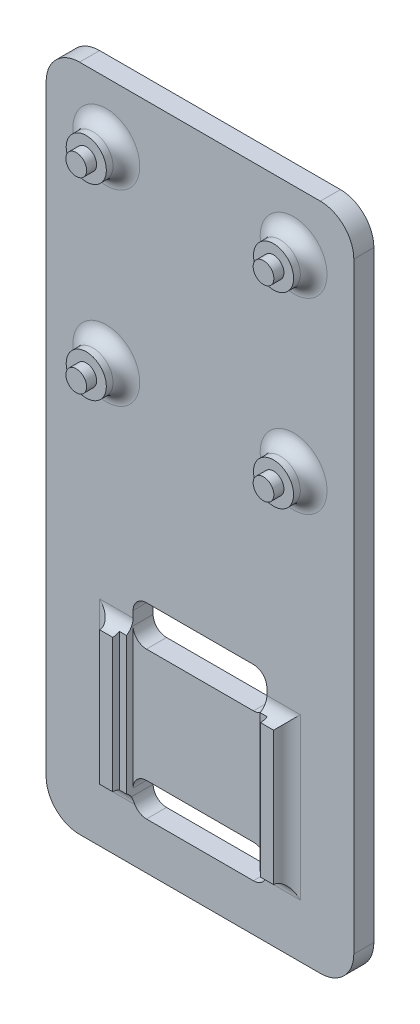
SolidWorks part; units mm, degrees
ref_plane "正面" through (0, 0, 0) normal (0, 0, 1) x (1, 0, 0)
ref_plane "平面" through (0, 0, 0) normal (0, 1, 0) x (1, 0, 0)
ref_plane "右側面" through (0, 0, 0) normal (1, 0, 0) x (0, 0, -1)
sketch "ｽｹｯﾁ1" plane through (0, 0, 0) normal (0, 0, 1) x (1, 0, 0)
  line L1 (0, 0) -> (46, 0)
  line L2 (0, 0) -> (0, 100)
  line L3 (0, 100) -> (46, 100)
  line L4 (46, 0) -> (46, 100)
  dimension "D1" = 100
  dimension "D2" = 46
extrude "ﾎﾞｽ - 押し出し1" add sketch "ｽｹｯﾁ1" along normal blind 3
sketch "ｽｹｯﾁ2" plane through (0, 0, 3) normal (0, 0, 1) x (1, 0, 0)
  line L0 (23, 100) -> (23, 0) construction
  line L1 (9, 91) -> (37, 91) construction
  line L2 (9, 91) -> (9, 63) construction
  line L3 (9, 63) -> (37, 63) construction
  line L4 (37, 91) -> (37, 63) construction
  line L5 (46, 100) -> (0, 100) construction
  line L6 (0, 0) -> (46, 0) construction
  circle A0 centre (9, 91) radius 3
  circle A1 centre (37, 91) radius 3
  circle A2 centre (9, 63) radius 3
  circle A3 centre (37, 63) radius 3
  point P10 (23, 91)
  dimension "D4" = 6
  dimension "D5" = 6
  dimension "D6" = 6
  dimension "D7" = 6
  dimension "D1" = 28
  dimension "D2" = 28
  dimension "D3" = 9
extrude "ﾎﾞｽ - 押し出し2" add sketch "ｽｹｯﾁ2" along normal blind 3
sketch "ｽｹｯﾁ3" plane through (0, 0, 6) normal (0, 0, 1) x (1, 0, 0)
  circle A0 centre (9, 91) radius 1.55
  circle A1 centre (37, 91) radius 1.55
  circle A2 centre (9, 63) radius 1.55
  circle A3 centre (37, 63) radius 1.55
  dimension "D1" = 3.1
  dimension "D2" = 3.1
  dimension "D3" = 3.1
  dimension "D4" = 3.1
extrude "ﾎﾞｽ - 押し出し3" add sketch "ｽｹｯﾁ3" along normal blind 1.5
fillet "ﾌｨﾚｯﾄ1" radius 2 4 edges at (34, 63, 3) (6, 63, 3) (34, 91, 3) (6, 91, 3)
fillet "ﾌｨﾚｯﾄ2" radius 5 4 edges at (46, 0, 1.5) (0, 0, 1.5) (46, 100, 1.5) (0, 100, 1.5)
sketch "ｽｹｯﾁ4" plane through (0, 0, 3) normal (0, 0, 1) x (1, 0, 0)
  line L0 (23, 0) -> (23, 100) construction
  line L1 (5, 0) -> (41, 0) construction
  line L2 (41, 100) -> (5, 100) construction
  line L4 (12, 5) -> (34, 5) construction
  line L5 (12, 5) -> (12, 35) construction
  line L6 (12, 35) -> (34, 35) construction
  line L7 (34, 5) -> (34, 35) construction
  line L8 (12, 5) -> (34, 35) construction
  line L9 (12, 35) -> (34, 5) construction
  line L12 (12, 30) -> (10, 30)
  line L13 (12, 30) -> (12, 10)
  line L14 (12, 10) -> (10, 10)
  line L15 (10, 30) -> (10, 10)
  line L16 (12, 30) -> (10, 10) construction
  line L17 (12, 10) -> (10, 30) construction
  line L18 (34, 30) -> (36, 30)
  line L19 (34, 30) -> (34, 10)
  line L20 (34, 10) -> (36, 10)
  line L21 (36, 30) -> (36, 10)
  line L22 (34, 30) -> (36, 10) construction
  line L23 (34, 10) -> (36, 30) construction
  line L24 (12, 30) -> (13, 30)
  line L25 (12, 30) -> (12, 10)
  line L26 (12, 10) -> (13, 10)
  line L27 (13, 30) -> (13, 10)
  line L28 (12, 30) -> (13, 10) construction
  line L29 (12, 10) -> (13, 30) construction
  line L30 (34, 30) -> (33, 30)
  line L31 (34, 30) -> (34, 10)
  line L32 (34, 10) -> (33, 10)
  line L33 (33, 30) -> (33, 10)
  line L34 (34, 30) -> (33, 10) construction
  line L35 (34, 10) -> (33, 30) construction
  point P10 (23, 20)
  point P19 (11, 20)
  point P20 (35, 20)
  point P23 (12.5, 20)
  point P26 (33.5, 20)
  dimension "D1" = 22
  dimension "D2" = 30
  dimension "D3" = 5
  dimension "D4" = 20
  dimension "D5" = 2
  dimension "D6" = 1
  dimension "D7" = 10
extrude "ﾎﾞｽ - 押し出し4" add sketch "ｽｹｯﾁ4" along normal blind 2 contours L12 L15 L14 L13 | L27 L24 L13 L26 | L30 L33 L32 L19 | L21 L18 L19 L20 region at (11, 20, 3) region at (12.5, 20, 3) region at (35, 20, 3) region at (33.5, 20, 3)
sketch "ｽｹｯﾁ5" plane through (0, 0, 5) normal (0, 0, 1) x (1, 0, 0)
  line L0 (23, 0) -> (23, 100) construction
  line L1 (5, 0) -> (41, 0) construction
  line L2 (41, 100) -> (5, 100) construction
  line L4 (11.95, 35) -> (34.05, 35)
  line L5 (11.95, 35) -> (11.95, 5)
  line L6 (11.95, 5) -> (34.05, 5)
  line L7 (34.05, 35) -> (34.05, 5)
  line L8 (11.95, 35) -> (34.05, 5) construction
  line L9 (11.95, 5) -> (34.05, 35) construction
  point P10 (23, 20)
  dimension "D1" = 22.1
  dimension "D2" = 5
  dimension "D3" = 30
extrude "ｶｯﾄ - 押し出し1" cut sketch "ｽｹｯﾁ5" against normal blind 1
fillet "ﾌｨﾚｯﾄ3" radius 2 6 edges at (34.5, 10, 3) (36, 20, 3) (34.5, 30, 3) (11.5, 30, 3) (11.5, 10, 3) (10, 20, 3)
sketch "ｽｹｯﾁ6" plane through (0, 0, 3) normal (0, 0, 1) x (1, 0, 0)
  line L0 (23, 0) -> (23, 100) construction
  line L1 (13, 35) -> (33, 35)
  line L2 (13, 35) -> (13, 29)
  line L3 (13, 29) -> (33, 29)
  line L4 (33, 35) -> (33, 29)
  line L5 (13, 35) -> (33, 29) construction
  line L6 (13, 29) -> (33, 35) construction
  line L7 (5, 0) -> (41, 0) construction
  line L8 (41, 100) -> (5, 100) construction
  line L10 (13, 12) -> (33, 12)
  line L11 (13, 12) -> (13, 7)
  line L12 (13, 7) -> (33, 7)
  line L13 (33, 12) -> (33, 7)
  line L14 (13, 12) -> (33, 7) construction
  line L15 (13, 7) -> (33, 12) construction
  point P4 (23, 32)
  point P15 (23, 9.5)
  dimension "D1" = 20
  dimension "D2" = 5
  dimension "D3" = 7
  dimension "D4" = 6
  dimension "D5" = 29
  dimension "D6" = 20
extrude "ｶｯﾄ - 押し出し2" cut sketch "ｽｹｯﾁ6" against normal blind 10
fillet "ﾌｨﾚｯﾄ4" radius 2 8 edges at (33, 7, 1.5) (33, 12, 1.5) (13, 12, 1.5) (13, 7, 1.5) (13, 29, 1.5) (13, 35, 1.5) (33, 29, 1.5) (33, 35, 1.5)
